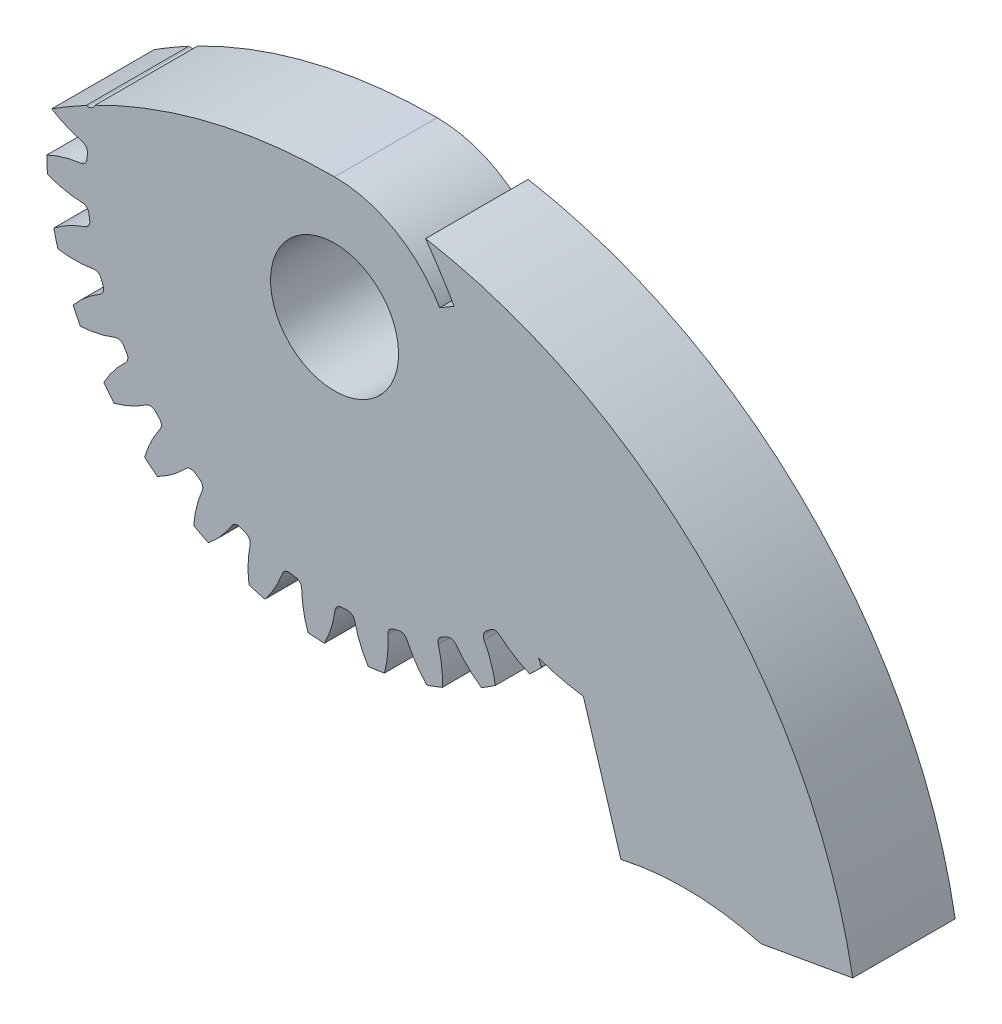
SolidWorks part; units mm, degrees
material "ABS"
ref_plane "Front" through (0, 0, 0) normal (0, 0, 1) x (1, 0, 0)
ref_plane "Top" through (0, 0, 0) normal (0, 1, 0) x (1, 0, 0)
ref_plane "Right" through (0, 0, 0) normal (1, 0, 0) x (0, 0, -1)
sketch "Sketch3" plane through (0, 0, 0) normal (0, 0, 1) x (1, 0, 0)
  circle A0 centre (0, 0) radius 40.64
  dimension "od" = 81.28
extrude "gearBody" add sketch "Sketch3" along normal blind 9.652
sketch "Sketch2" plane through (0, 0, 0) normal (0, 0, 1) x (1, 0, 0)
  line L0 (0, 0) -> (34.0786, 14.1158) construction
  line L1 (45.4751, -11.4855) -> (0, 0) construction
  line L2 (0, 0) -> (36.3143, 0) construction
  line L3 (38.0972, -0.458) -> (37.8451, -4.4001) construction
  line L5 (37.9712, -2.4291) -> (0, 0) construction
  line L7 (0, 0) -> (36.8864, 0) construction
  arc A0 (36.879, -0.7403) -> (36.6727, -3.9649) centre (0, 0) ccw construction
  arc A1 (40.637, 0.4947) -> (40.2427, -5.6687) centre (0, 0) ccw construction
  arc A2 (38.0972, -0.458) -> (37.8451, -4.4001) centre (0, 0) ccw construction
  arc A3 (34.9015, -2.6404) -> (34.9534, -1.8283) centre (0, 0) ccw
  arc A4 (45.4751, -11.4855) -> (35.6466, -3.6712) centre (32.0022, -18.3431) ccw
  arc A5 (45.4751, -11.4855) -> (46.5679, 5.5974) centre (0, 0) ccw
  arc A6 (46.5679, 5.5974) -> (35.8238, -0.9008) centre (34.0786, 14.1158) cw
  arc A7 (34.9534, -1.8283) -> (35.8238, -0.9008) centre (35.9376, -1.8798) cw
  arc A8 (35.6466, -3.6712) -> (34.9015, -2.6404) centre (35.8842, -2.7147) cw
  point P6 (46.5679, 5.5974)
  point P22 (45.4751, -11.4855)
  dimension "baseDia" = 73.7729
  dimension "od" = 81.28
  dimension "pd" = 76.2
  dimension "rd" = 70.0024
  dimension "rFillet" = 0.9855
  dimension "pointX" = 46.5679
  dimension "pointY" = 5.5974
  dimension "CTT" = 3.9421
  dimension "flankCenterAngle" = 22.5
extrude "toothCut" cut sketch "Sketch2" along normal through all
pattern_circular "CirPattern1" count 30 over 360 about axis through (0, 0, 9.652) along (0, 0, -1) of "toothCut"
scale "Scale1" scale about centroid uniform scaling no x scale factor 0.666667 y scale factor 0.666667 z scale factor 1
sketch "hub1Dia" plane through (0, 0, 0) normal (0, 0, -1) x (-1, 0, 0)
  circle A0 centre (0, 0) radius 12.7
  dimension "hub1Dia" = 25.4
sketch "hub2Dia" plane through (0, 0, 9.652) normal (0, 0, 1) x (1, 0, 0)
  circle A0 centre (0, 0) radius 12.7
  dimension "hub2dia" = 25.4
sketch "boreDia" plane through (0, 0, 0) normal (0, 0, 1) x (1, 0, 0)
  circle A0 centre (0, 0) radius 6.0255
  dimension "boreDia" = 12.051
extrude "bore" cut sketch "boreDia" against normal mid plane 25400
sketch "Sketch4" plane through (0, 0, 9.652) normal (0, 0, 1) x (1, 0, 0)
  circle A0 centre (0, -38.1) radius 49.53
  arc A2 (-27.1267, 3.3411) -> (27.1267, 3.3411) centre (0, 0) cw
  dimension "D1" = 99.06
  dimension "D2" = 38.1
extrude "Cut-Extrude1" cut sketch "Sketch4" against normal through all contours A0 region at (0, 16.3548, 9.652)
sketch "Sketch5" plane through (0, 0, 9.652) normal (0, 0, 1) x (1, 0, 0)
  line L0 (0, -38.1) -> (49.53, -38.1) construction
  line L1 (0, 0) -> (0, -38.1) construction
  line L2 (0, -38.1) -> (-24.765, 4.7942) construction
  line L3 (0, -38.1) -> (42.8942, -62.865) construction
  line L4 (23.4248, -19.2156) -> (26.9592, -30.742)
  line L6 (48.7775, -29.4992) -> (0, -38.1) construction
  line L7 (40.1449, -31.0214) -> (48.7775, -29.4992)
  circle A0 centre (0, -38.1) radius 49.53 construction
  circle A2 centre (0, -38.1) radius 14.3933 construction
  circle A3 centre (32.9956, -57.15) radius 27.0891 construction
  arc A4 (26.9592, -30.742) -> (40.1449, -31.0214) centre (32.9956, -57.15) cw
  arc A5 (48.7775, -29.4992) -> (8.0038, 10.779) centre (0, -38.1) ccw
  arc A6 (24.6567, 4.8566) -> (-22.5513, 5.9983) centre (0, -38.1) ccw construction
  spline S0 degree 2 poles (8.0038, 10.779) (4.7007, -16.4877) (23.4248, -19.2156) knots 0 0 0 1 1 1
  point P16 (50.0599, -29.2731)
  point P20 (51.8894, -28.9505)
  point P21 (48.7775, -29.4992)
  point P22 (48.7775, -29.4992)
  dimension "D2" = 28.7867
  dimension "D4" = 54.1782
  dimension "D1" = 120
  dimension "D3" = 120
  dimension "D5" = 38.1
  dimension "D6" = 80
extrude "Boss-Extrude1" add sketch "Sketch5" against normal up to surface (9.652 mm away) up to face at (6.0255, 0, 0)
sketch "Sketch6" plane through (0, 0, 9.652) normal (0, 0, 1) x (1, 0, 0)
  line L0 (0, 0) -> (-32.9956, -19.05) construction
  line L1 (0, 0) -> (0, -38.1) construction
  line L2 (-32.9956, -19.05) -> (0, 0) construction
  line L3 (11.2625, 6.5024) -> (9.8987, 5.715)
  circle A0 centre (-32.9956, -19.05) radius 49.53 construction
  circle A1 centre (-32.9956, -19.05) radius 51.1048 construction
  arc A3 (48.7775, -29.4992) -> (-22.5513, 5.9983) centre (0, -38.1) ccw construction
  arc A4 (11.2625, 6.5024) -> (8.5694, 10.6831) centre (-32.9956, -19.05) ccw
  circle A5 centre (0, -38.1) radius 49.53 construction
  arc A6 (8.5694, 10.6831) -> (0, 11.43) centre (0, -38.1) ccw
  arc A7 (9.8987, 5.715) -> (0, 11.43) centre (0, 0) ccw
  point P18 (-0.097, 11.4299)
  dimension "D1" = 99.06
  dimension "D4" = 102.2096
  dimension "D2" = 60
  dimension "D3" = 38.1
extrude "Body Tube Cut Out" cut sketch "Sketch6" against normal through all
equation "\"Aft_Section_Length\" = 32in"
equation "\"Mid_Coupler_Length\" = 12in"
equation "\"AB_Coupler_OD_Length\"= 1in"
equation "\"AB_Coupling_Section_Length\"= 0.375in"
equation "\"AB_Coupler_Length\"= \"AB_Coupler_OD_Length\" + \"AB_Coupling_Section_Length\" * 2"
equation "\"Cutout_Angle\" = 60"
equation "\"AB_Paddle_Height\" = 0.375in"
equation "\"AB_Coupler_Num_Screws\"= 4"
equation "\"Num_Cutouts\" = 4"
equation "\"AB_Coupler_OD\"= 4.024in"
equation "\"AB_Coupler_ID\"= 3.7in"
equation "\"AB_Coupler_Surface_Diameter\"= 3.899in"
equation "\"AB_Coupling_Screw_Diameter\"= 0.1065in"
equation "\"AB_Central_Bushing_Length\" = 0.75in"
equation "\"Lead_Screw_Dist\" = 2in"
equation "\"Lead_Screw_Diam\" = 0.375in"
equation "\"Lead_Screw_Length\" = \"Mid_Coupler_Length\" + 2*0.375in + 2*0.5in"
equation "\"Paddle_Pin_Offset\" = 0.25in"
equation "\"Paddle_Pin_Radius\" = 2.25*2/3in"
equation "\"Fwd_BKHD_From_Top\" = 18in"
equation "\"D1@Sketch4\"=\"Body_Tube_ID\""
equation "\"D2@Sketch4\"=\"Paddle_Pin_Radius\""
equation "\"Motor_OD\" = 54.4mm"
equation "\"Paddle_Gear_OD\" = 3.2in"
equation "\"Drive_Gear_OD\" = 1.7*2/3in"
equation "\"Fin_Thickness\" = 0.118in"
equation "\"DB9_Hole_Dist\" = 25mm"
equation "\"Motor_Length\" = 401mm"
equation "\"Body_Tube_OD\"= 4.024in"
equation "\"Body_Tube_ID\"= 3.90in"
equation "\"Coupler_OD\" = 3.899in"
equation "\"Coupler_ID\" = 3.755in"
equation "\"Fwd_Section_Length\" = 20in"
equation "\"Mid_Section_Length\" = 4in"
equation "\"Aft_Upper_Tube_Length\" = 10in"
equation "\"Aft_Lower_Tube_Length\" = 18in"
equation "\"Nosecone_Coupler_Length\" = 5in"
equation "\"Avionics_Bulkhead_Thickness\" = 0.25in"
equation "\"Avionics_Bulkhead_Lip\" = 0.125in"
equation "\"Avionics_Board_Length\" = \"Mid_Coupler_Length\" - 2*\"Avionics_Bulkhead_Lip\""
equation "\"Lead_Screw_Hole_Diam\" = 0.386in"
equation "\"Centering_Ring_Cutout_Dia\"=1.5in"
equation "\"Airbrakes_Wire_Hole_Dist\" = 1.1in"
equation "\"Airbrakes_Wire_Hole_Dia\" = 0.25in"
equation "\"DB9_Relief_Width\" = 0.47in"
equation "\"DB9_Relief_Hole_Offset\" = 0.09in"
equation "\"Servo_Gear_Offset\" = 0.5in"
equation "\"D2@Sketch5\"=\"Drive_Gear_OD\""
equation "\"D5@Sketch5\"=\"Paddle_Pin_Radius\""
equation "\"D1@Sketch6\"=\"Body_Tube_ID\""
equation "\"D2@Sketch6\"=60"
equation "\"D3@Sketch6\"=\"Paddle_Pin_Radius\""
equation "\"D4@Sketch6\"=\"Body_Tube_OD\""
equation "\"Airbrake_Shaft_Diameter\"= 12.051mm"
equation "\"boreDia@boreDia\"=\"Airbrake_Shaft_Diameter\""
